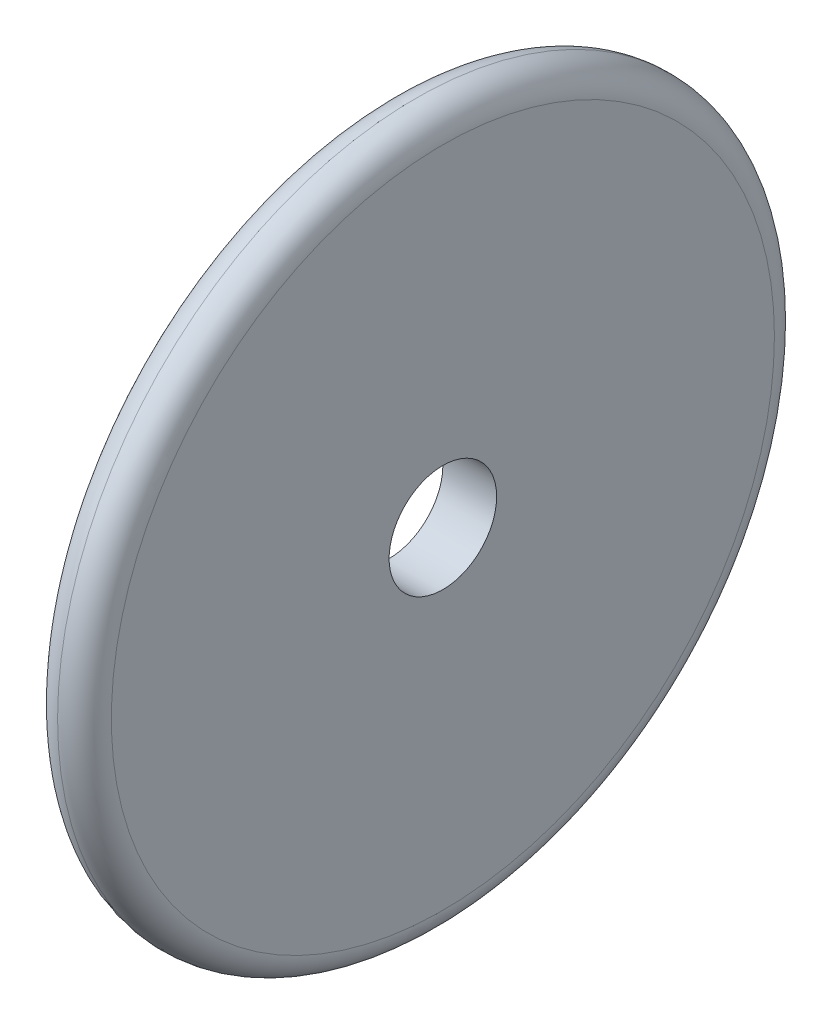
SolidWorks part; units mm, degrees
ref_plane "Front Plane" through (0, 0, 0) normal (1, 0, 0) x (0, 1, 0)
ref_plane "Top Plane" through (0, 0, 0) normal (0, 0, 1) x (0, 1, 0)
ref_plane "Right Plane" through (0, 0, 0) normal (0, 1, 0) x (-1, 0, 0)
sketch "Sketch1" plane through (0, 0, 0) normal (1, 0, 0) x (0, 1, 0)
  circle A0 centre (0, 0) radius 10
  circle A1 centre (0, 0) radius 1.5
  dimension "D1" = 20
  dimension "D2" = 3
extrude "Boss-Extrude1" add sketch "Sketch1" along normal blind 1.5
fillet "Fillet1" radius 0.75 2 edges at (1.5, 0, -10) (0, 0, -10)
